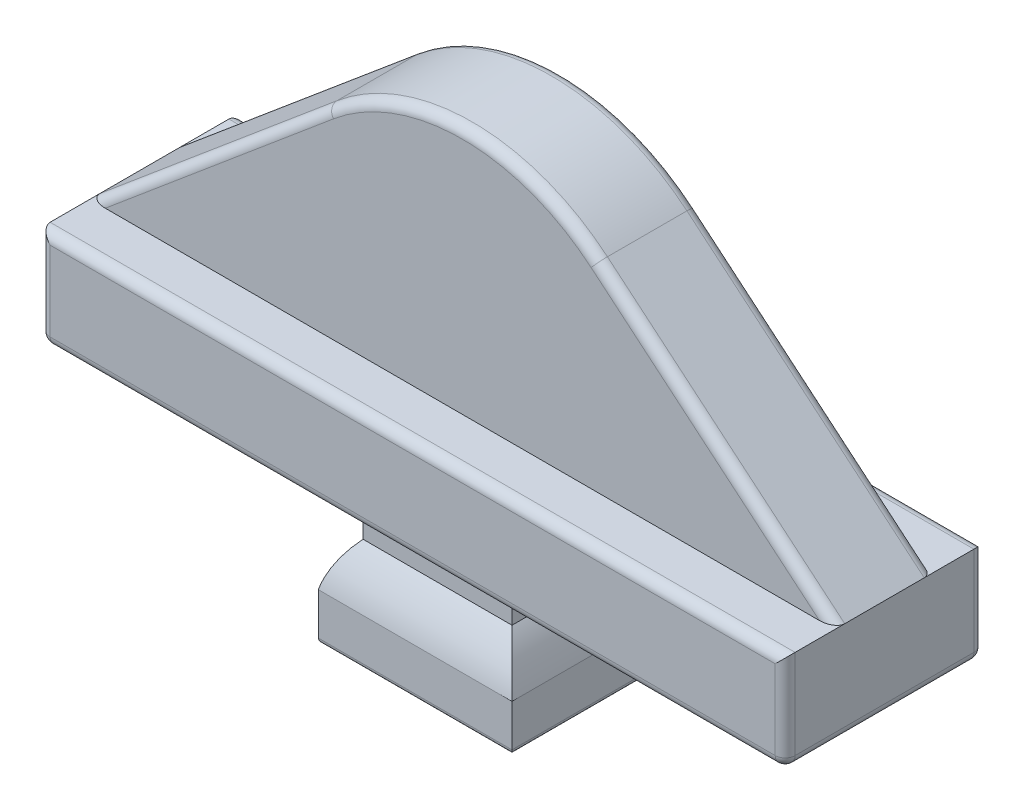
SolidWorks part; units mm, degrees
ref_plane "前视基准面" through (0, 0, 0) normal (0, 0, 1) x (1, 0, 0)
ref_plane "上视基准面" through (0, 0, 0) normal (0, 1, 0) x (1, 0, 0)
ref_plane "右视基准面" through (0, 0, 0) normal (1, 0, 0) x (0, 0, -1)
sketch "草图1" plane through (0, 0, 0) normal (0, 0, 1) x (1, 0, 0)
  line L0 (7.5, 1) -> (7.5, -1)
  line L1 (7.5, 1) -> (-7.5, 1)
  line L2 (7.5, -1) -> (-7.5, -1)
  line L3 (-7.5, 1) -> (-7.5, -1)
  line L4 (7.5, 1) -> (-7.5, -1) construction
  line L5 (7.5, -1) -> (-7.5, 1) construction
  point P1 (0, 0)
  dimension "D1" = 2
  dimension "D2" = 15
extrude "凸台-拉伸1" add sketch "草图1" along normal blind 2 and the other way blind 2
sketch "草图2" plane through (0, 0, 0) normal (0, 0, 1) x (1, 0, 0)
  line L0 (0, -1) -> (0, -3) construction
  line L1 (-7.5, -1) -> (7.5, -1) construction
  line L2 (0, -3) -> (0, -3.5) construction
  line L3 (-1.5, -1) -> (1.5, -1)
  line L4 (1.5, -1) -> (1.5, -1.6771)
  line L5 (-1.95, -3.5) -> (1.95, -3.5)
  line L6 (1.95, -3.5) -> (1.95, -2.5556)
  line L7 (-1.95, -3.5) -> (-1.95, -2.5556)
  line L8 (-1.5, -1) -> (-1.5, -1.6771)
  arc A0 (1.95, -2.5556) -> (1.5, -1.6771) centre (0, -3) ccw
  arc A1 (-1.95, -2.5556) -> (-1.5, -1.6771) centre (0, -3) cw
  dimension "D5" = 2
  dimension "D1" = 2
  dimension "D2" = 0.5
  dimension "D3" = 1.5
  dimension "D4" = 1.95
extrude "凸台-拉伸2" add sketch "草图2" along normal blind 2 and the other way blind 2
sketch "草图3" plane through (0, 0, 0) normal (1, 0, 0) x (0, 0, -1)
  line L0 (0, -1) -> (0, -3) construction
  line L1 (2, -1) -> (-2, -1) construction
  line L2 (0, -3) -> (0, -3.5) construction
  line L3 (2, -3.5) -> (-2, -3.5) construction
  line L4 (0, -1) -> (1.5, -1) construction
  line L5 (1.5, -1) -> (1.5, -1.6771)
  line L6 (0, -3.5) -> (1.95, -3.5) construction
  line L7 (1.95, -3.5) -> (1.95, -2.5556)
  line L8 (1.95, -3.5) -> (2, -3.5)
  line L9 (2, -3.5) -> (2, -1)
  line L10 (2, -1) -> (1.5, -1)
  line L11 (-2, -1) -> (-1.5, -1)
  line L12 (-1.5, -1) -> (-1.5, -1.6771)
  line L13 (-2, -3.5) -> (-2, -1)
  line L14 (-1.95, -3.5) -> (-1.95, -2.5556)
  line L15 (-1.95, -3.5) -> (-2, -3.5)
  arc A0 (1.95, -2.5556) -> (1.5, -1.6771) centre (0, -3) ccw
  arc A1 (-1.95, -2.5556) -> (-1.5, -1.6771) centre (0, -3) cw
  dimension "D1" = 2
  dimension "D2" = 1.5
  dimension "D3" = 1.95
extrude "切除-拉伸1" cut sketch "草图3" against normal blind 2 and the other way blind 2
sketch "草图4" plane through (0, 0, 0) normal (0, 0, 1) x (1, 0, 0)
  line L0 (7.5, 1) -> (-7.5, 1)
  line L1 (-7.5, 1) -> (-2.7219, 5.0093)
  line L2 (7.5, 1) -> (2.7219, 5.0093)
  line L3 (0, 1) -> (0, 6) construction
  arc A1 (2.7219, 5.0093) -> (-2.7219, 5.0093) centre (0, 1.7655) ccw
  dimension "D1" = 40
  dimension "D2" = 40
  dimension "D3" = 5
extrude "凸台-拉伸3" add sketch "草图4" along normal blind 1 and the other way blind 1
fillet "圆角2" radius 0.2 8 edges at (0, 1, -2) (-7.5, 0, -2) (7.5, 0, -2) (-7.5, 0, 2) (0, 1, 2) (7.5, 0, 2)
fillet "圆角4" radius 0.2 6 edges at (7.4414, -0.9414, -1.9414) (7.4414, -0.9414, 1.9414) (-7.4414, -0.9414, -1.9414) (-7.4414, -0.9414, 1.9414) (7.5, -1, 0) (-7.5, -1, 0)
fillet "圆角5" radius 0.2 6 edges at (0, 6, -1) (0, 6, 1)
fillet "圆角7" radius 0.1 4 edges at (0, -3.5, 1.95) (1.95, -3.5, 0) (0, -3.5, -1.95) (-1.95, -3.5, 0)
